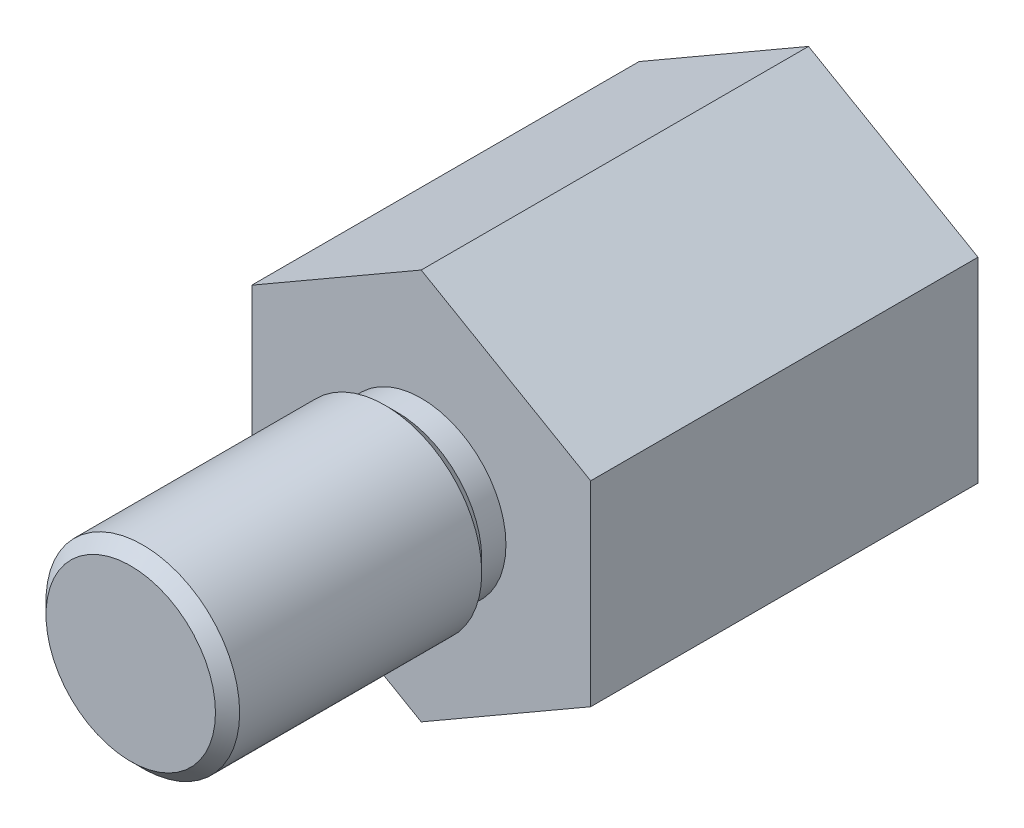
SolidWorks part; units mm, degrees
ref_plane "Спереди" through (0, 0, 0) normal (0, 0, 1) x (1, 0, 0)
ref_plane "Сверху" through (0, 0, 0) normal (0, 1, 0) x (1, 0, 0)
ref_plane "Справа" through (0, 0, 0) normal (1, 0, 0) x (0, 0, -1)
sketch "Эскиз1" plane through (0, 0, 0) normal (0, 0, 1) x (1, 0, 0)
  line L1 (0, 4.0415) -> (-3.5, 2.0207)
  line L2 (-3.5, 2.0207) -> (-3.5, -2.0207)
  line L3 (-3.5, -2.0207) -> (0, -4.0415)
  line L4 (0, -4.0415) -> (3.5, -2.0207)
  line L5 (3.5, -2.0207) -> (3.5, 2.0207)
  line L6 (3.5, 2.0207) -> (0, 4.0415)
  circle A0 centre (0, 0) radius 3.5 construction
  dimension "D1" = 7
extrude "Вытянуть1" add sketch "Эскиз1" along normal blind 8
sketch "Эскиз2" plane through (0, 0, 8) normal (0, 0, 1) x (1, 0, 0)
  circle A0 centre (0, 0) radius 2
  dimension "D1" = 4
extrude "Вытянуть2" add sketch "Эскиз2" along normal blind 6
cosmetic thread "Условное изображение резьбы3"
sketch "Эскиз3" plane through (0, 0, 8) normal (0, 0, 1) x (1, 0, 0)
  circle A0 centre (0, 0) radius 1.75
  circle A1 centre (0, 0) radius 2 construction
  circle A2 centre (0, 0) radius 2
  dimension "D1" = 3.5
extrude "Вырез-Вытянуть3" cut sketch "Эскиз3" along normal blind 0.5
chamfer "Фаска1" distance 0.25 angle 45 2 edges at (2, 0, 8.5) (2, 0, 14)
hole_wizard "Отверстие с зазором M41" positions "Трехмерный эскиз2" profile "Эскиз5" hole size "M4" standard "Ansi Метрический"
sketch3d "Трехмерный эскиз2"
  point P0 (0, 0, 0)
  point P2 (0, 0, 0)
  point P3 (0, 0, 0)
sketch "Эскиз5" plane through (0, 0, 0) normal (1, 0, 0) x (0, 1, 0)
  line L0 (0, 0) -> (0, 6.9914)
  line L1 (0, 6.9914) -> (1.65, 6)
  line L2 (1.65, 6) -> (1.65, 0.35)
  line L3 (1.65, 0.35) -> (2, 0)
  line L5 (2, 0) -> (0, 0)
  line L6 (-1.65, 0.35) -> (-2, 0) construction
  line L10 (0, 6.9914) -> (-1.65, 6) construction
  line L11 (0, -6.35) -> (0, 107.95) construction
  dimension "Диаметр отверстия" = 3.3
  dimension "Глубина отверстия" = 6
  dimension "Диаметр передней зенковки" = 4
  dimension "Угол передней зенковки" = 90
  dimension "Угол заточки сверла" = 118
cosmetic thread "Условное изображение резьбы1" parameters "D1"=5, "D2"=4
